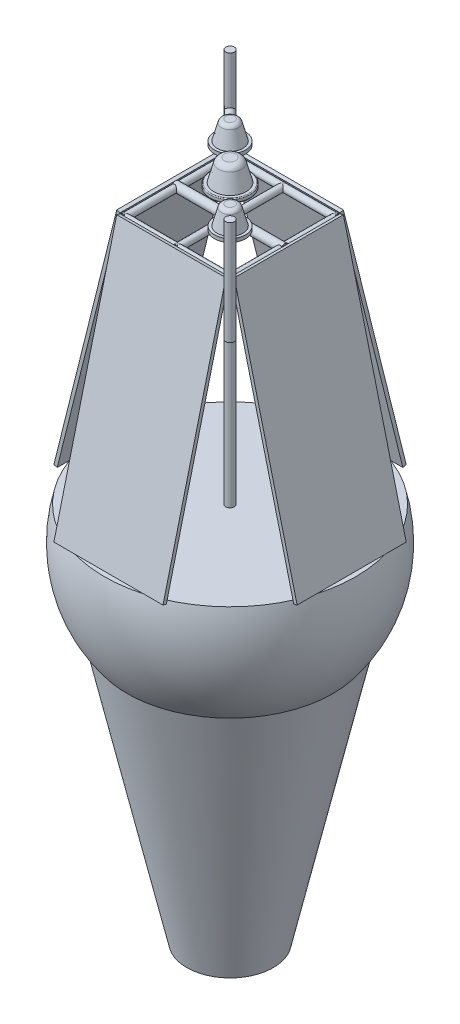
SolidWorks part; units mm, degrees
other "Cámara1"
other "Cámara2"
other "Cámara3"
ref_plane "Alzado" through (0, 0, 0) normal (0, 0, 1) x (1, 0, 0)
ref_plane "Planta" through (0, 0, 0) normal (0, 1, 0) x (1, 0, 0)
ref_plane "Vista lateral" through (0, 0, 0) normal (1, 0, 0) x (0, 0, -1)
sketch "Croquis1" plane through (0, 0, 0) normal (0, 0, 1) x (1, 0, 0)
  line L0 (25, 192.0286) -> (725, 192.0286)
  line L1 (0, 1742.0286) -> (0, -750) construction
  line L2 (0, 1742.0286) -> (0, -750) construction
  line L3 (25, 192.0286) -> (25, 1742.0286)
  line L4 (25, 1742.0286) -> (0, 1742.0286)
  line L5 (702.2888, 196.8671) -> (339.4059, 1652.3107) construction
  line L6 (339.4059, 1652.3107) -> (320, 1647.4722) construction
  line L7 (320, 1647.4722) -> (682.8828, 192.0286) construction
  line L8 (682.8828, 192.0286) -> (702.2888, 196.8671) construction
  line L9 (0, 1742.0286) -> (0, -2000)
  line L10 (0, -2000) -> (250, -2000)
  line L11 (250, -2000) -> (594.3574, -457.4268)
  arc A0 (0, -750) -> (725, 192.0286) centre (0, 0) ccw construction
  arc A1 (725, 192.0286) -> (594.3574, -457.4268) centre (0, 0) cw
  dimension "D1" = 1500
  dimension "D2" = 1450
  dimension "D3" = 20
  dimension "D4" = 1500
  dimension "D5" = 25
  dimension "D6" = 1550
  dimension "D7" = 76
  dimension "D8" = 320
  dimension "D9" = 250
  dimension "D10" = 2000
revolve "Revolución1" add sketch "Croquis1" angle 360 about L2
sketch "Croquis3" plane through (0, 0, 0) normal (0, 0, 1) x (1, 0, 0)
  line L0 (339.4059, 1652.3107) -> (320, 1647.4722) construction
  line L1 (702.2888, 196.8671) -> (339.4059, 1652.3107) construction
  line L2 (320, 1647.4722) -> (682.8828, 192.0286) construction
  line L3 (682.8828, 192.0286) -> (702.2888, 196.8671) construction
  line L4 (339.4059, 1652.3107) -> (320, 1647.4722)
  line L5 (702.2888, 196.8671) -> (339.4059, 1652.3107)
  line L6 (320, 1647.4722) -> (322.5706, 1637.1621)
  line L7 (682.8828, 192.0286) -> (702.2888, 196.8671)
  line L8 (320, 1647.4722) -> (304.3743, 1647.4722) construction
  line L9 (322.5706, 1637.1621) -> (321.9544, 1637.0085)
  line L10 (304.3743, 1627.4722) -> (323.7802, 1632.3107) construction
  line L11 (324.3736, 1627.3056) -> (324.9898, 1627.4592)
  line L12 (324.9898, 1627.4592) -> (682.8828, 192.0286)
  arc A0 (321.9544, 1637.0085) -> (324.3736, 1627.3056) centre (304.3743, 1627.4722) ccw
  dimension "D1" = 40
  dimension "D2" = 10
extrude "Saliente-Extruir1" add sketch "Croquis3" along normal mid plane 630
pattern_circular "MatrizC13" count 4 over 360 about axis through (0, 1742.0286, 0) along (0, 1, 0) of bodies 102
sketch "Croquis4" plane through (0, 0, 0) normal (0, 0, 1) x (1, 0, 0)
  line L0 (-315, 1627.4592) -> (315, 1627.4592) construction
  circle A0 centre (0, 1627.4592) radius 20
  arc A1 (321.9544, 1637.0085) -> (324.3736, 1627.3056) centre (304.3743, 1627.4722) ccw construction
extrude "Saliente-Extruir15" add sketch "Croquis4" along normal mid plane 630 separate body
ref_plane "Plano4" through (0, 1742.03, 0) normal (0, 1, 0) x (1, 0, 0)
sketch "Croquis5" plane through (0, 0, 0) normal (1, 0, 0) x (0, 0, -1)
  line L0 (-315, 1627.4592) -> (315, 1627.4592) construction
  line L1 (25, 192.0286) -> (25, 1742.0286) construction
  circle A0 centre (0, 1627.4592) radius 25
extrude "Saliente-Extruir17" add sketch "Croquis5" along normal mid plane 630 separate body
sketch "Croquis6" plane through (0, 1742.0286, 0) normal (0, 1, 0) x (1, 0, 0)
  line L0 (-750, -750) -> (750, 750) construction
  line L1 (0, 0) -> (750, 0) construction
  line L2 (750, 0) -> (750, 750) construction
  line L3 (-750, 750) -> (0, 0) construction
  circle A1 centre (0, 0) radius 750 construction
ref_plane "Plano1" through (-0.0001, 0, -0.0001) normal (0.7071, 0, 0.7071) x (0.7071, 0, -0.7071)
sketch "Croquis7" plane through (-0.0001, 0, -0.0001) normal (0.7071, 0, 0.7071) x (0.7071, 0, -0.7071)
  line L0 (-25, 1742.0286) -> (25, 1742.0286) construction
  line L1 (25, 192.0286) -> (25, 1742.0286) construction
  circle A0 centre (0, 1742.0286) radius 25
extrude "Saliente-Extruir18" add sketch "Croquis7" along normal mid plane 1200
ref_plane "Plano2" through (0.0001, 0, -0.0001) normal (-0.7071, 0, 0.7071) x (0.7071, 0, 0.7071)
sketch "Croquis9" plane through (-1096.0155, 1742.03, 1096.0155) normal (0, 1, 0) x (0.7071, 0, 0.7071)
  line L0 (600, 1525) -> (600, 1575) construction
  line L1 (-600, 1575) -> (-600, 1525) construction
  line L2 (0, 1525) -> (600, 1525) construction
  circle A0 centre (600, 1550) radius 25
  circle A1 centre (-600, 1550) radius 25
extrude "Saliente-Extruir19" add sketch "Croquis9" along normal mid plane 600
sketch "Croquis11" plane through (0.0001, 0, -0.0001) normal (-0.7071, 0, 0.7071) x (0.7071, 0, 0.7071)
  line L0 (-600, 1742.0287) -> (600.0001, 1742.0287) construction
  line L1 (304, 1797.0287) -> (304, 1887.0287)
  line L2 (304, 1887.0287) -> (300, 1887.0287)
  line L5 (-575, 1767.0287) -> (-600, 1742.0287) construction
  line L6 (-575, 1717.0287) -> (-600, 1742.0287) construction
  line L7 (600, 1742.0286) -> (575, 1717.0286) construction
  line L8 (300, 1742.0287) -> (300, 1907.0287) construction
  line L9 (300, 1907.0287) -> (325.8168, 1907.0287)
  line L10 (349.965, 1888.4992) -> (374.4744, 1797.0287)
  line L11 (374.4744, 1797.0287) -> (390, 1797.0287)
  line L12 (390, 1797.0287) -> (390, 1777.0287)
  line L13 (390, 1777.0287) -> (310, 1777.0287)
  line L15 (310, 1777.0287) -> (310, 1742.0287)
  line L16 (310, 1742.0287) -> (300, 1742.0287)
  line L17 (575, 2042.03) -> (575, 1767.0286) construction
  line L18 (300, 1907.0287) -> (300, 1902.0287)
  line L19 (300, 1902.0287) -> (325.8168, 1902.0287)
  line L20 (345.1353, 1887.2051) -> (369.298, 1797.0287)
  line L21 (369.298, 1797.0287) -> (304, 1797.0287)
  line L22 (300, 1887.0287) -> (300, 1742.0287)
  arc A0 (325.8168, 1902.0287) -> (345.1353, 1887.2051) centre (325.8168, 1882.0287) cw
  arc A1 (325.8168, 1907.0287) -> (349.965, 1888.4992) centre (325.8168, 1882.0287) cw
  point P26 (345, 1907.0287)
  dimension "D11" = 20
  dimension "D12" = 25
  dimension "D1" = 20
  dimension "D2" = 35
  dimension "D3" = 275
  dimension "D4" = 90
  dimension "D5" = 15
  dimension "D6" = 180
  dimension "D7" = 20
  dimension "D8" = 130
  dimension "D9" = 5
  dimension "D10" = 5
  dimension "D13" = 8
  dimension "D14" = 90
revolve "Revolución2" add sketch "Croquis11" angle 360 about L8
sketch "Croquis13" plane through (0.0001, 0, -0.0001) normal (-0.7071, 0, 0.7071) x (0.7071, 0, 0.7071)
  line L0 (300, 1887.0287) -> (300, 1842.0287) construction
  line L1 (304, 1887.0287) -> (296, 1887.0287) construction
  line L2 (300, 1842.0287) -> (310.4323, 1842.0287) construction
  line L4 (300, 1844.5287) -> (307, 1844.5287)
  line L5 (310.4323, 1842.0287) -> (300, 1842.0287)
  line L6 (300, 1842.0287) -> (300, 1844.5287)
  line L7 (345.1353, 1887.2051) -> (254.8647, 1887.2051) construction
  arc A0 (318.5344, 1887.2051) -> (310.4323, 1842.0287) centre (440.4323, 1842.0287) ccw
  arc A1 (318.5344, 1887.2051) -> (307, 1844.5287) centre (400.9667, 1842.0287) ccw
  dimension "D3" = 94
  dimension "D4" = 130
  dimension "D1" = 45
  dimension "D2" = 5
  dimension "D5" = 7
revolve "Revolución4" add sketch "Croquis13" angle 360 about L5
mirror "Simetría1" about plane through (-0.0001, 0, -0.0001) normal (0.7071, 0, 0.7071) of "Revolución4", "Revolución2"
sketch "Croquis12" plane through (0.0001, 0, -0.0001) normal (-0.7071, 0, 0.7071) x (0.7071, 0, 0.7071)
  line L0 (0, 1717.0286) -> (0, 1927.0287) construction
  line L1 (25, 1717.0286) -> (575, 1717.0286) construction
  line L2 (0, 1927.0287) -> (-33.1436, 1927.0287)
  line L3 (-66.951, 1901.0873) -> (-93.4936, 1802.0287)
  line L4 (-93.4936, 1802.0287) -> (-110, 1802.0287)
  line L5 (-115, 1797.0287) -> (-115, 1782.0287)
  line L6 (-110, 1777.0287) -> (-15, 1777.0287)
  line L7 (-15, 1777.0287) -> (-15, 1767.0286)
  line L8 (-15, 1767.0286) -> (0, 1767.0286)
  line L9 (0, 1767.0286) -> (0, 1927.0287)
  line L10 (290, 1767.0286) -> (-290, 1767.0287) construction
  line L11 (-390, 1777.0287) -> (-210, 1777.0287) construction
  line L12 (250.035, 1888.4992) -> (225.5256, 1797.0287) construction
  arc A0 (-33.1436, 1927.0287) -> (-66.951, 1901.0873) centre (-33.1436, 1892.0287) ccw
  arc A1 (-110, 1802.0287) -> (-115, 1797.0287) centre (-110, 1797.0287) ccw
  arc A2 (-115, 1782.0287) -> (-110, 1777.0287) centre (-110, 1782.0287) ccw
  point P20 (-60, 1927.0287)
  dimension "D6" = 35
  dimension "D7" = 5
  dimension "D1" = 25
  dimension "D2" = 120
  dimension "D3" = 150
  dimension "D4" = 30
  dimension "D5" = 230
revolve "Revolución3" add sketch "Croquis12" angle 360 about L0
